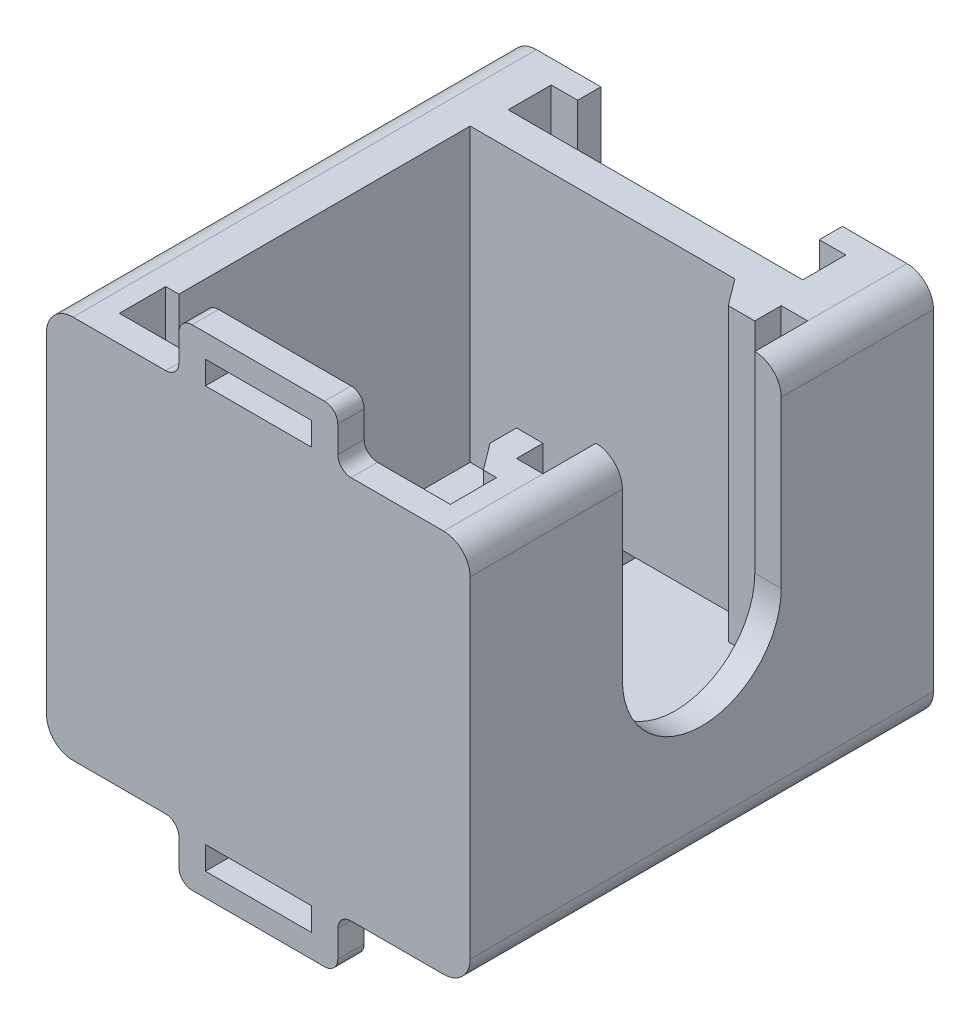
SolidWorks part; units mm, degrees
material "UNOBTANIUM"
ref_plane "Top Plane" through (0, 0, 0) normal (0, 0, 1) x (1, 0, 0)
ref_plane "Right Plane" through (0, 0, 0) normal (0, 1, 0) x (1, 0, 0)
ref_plane "Front Plane" through (0, 0, 0) normal (1, 0, 0) x (0, 0, -1)
ref_axis "x-axis" through (-17.6, 0, 0) along (1, 0, 0)
ref_axis "y-axis" through (0, -14.85, 0) along (0, 1, 0)
ref_axis "z-axis" through (0, 0, 36.75) along (0, 0, -1)
sketch "Sketch1" plane through (0, 0, 0) normal (0, 0, 1) x (1, 0, 0)
  line L1 (-16, 14.5) -> (16, 14.5)
  line L2 (-16, 14.5) -> (-16, -14.5)
  line L3 (-16, -14.5) -> (16, -14.5)
  line L4 (16, 14.5) -> (16, -14.5)
  line L5 (-16, 14.5) -> (16, -14.5) construction
  line L6 (-16, -14.5) -> (16, 14.5) construction
  point P0 (0, 0)
  dimension "D1" = 32
  dimension "D2" = 29
extrude "Boss-Extrude1" add sketch "Sketch1" along normal blind 35
fillet "Fillet1" radius 2 4 edges at (16, -14.5, 17.5) (16, 14.5, 17.5) (-16, -14.5, 17.5) (-16, 14.5, 17.5)
sketch "Sketch2" plane through (0, -14.5, 0) normal (0, -1, 0) x (1, 0, 0)
  line L0 (-9.125, 0) -> (-9.125, 1.75)
  line L1 (-14, 0) -> (14, 0) construction
  line L2 (-9.125, 1.75) -> (-11.125, 1.75)
  line L3 (-11.125, 1.75) -> (-11.125, 5)
  line L4 (-11.125, 5) -> (11.125, 5)
  line L5 (11.125, 5) -> (11.125, 1.75)
  line L6 (11.125, 1.75) -> (9.125, 1.75)
  line L7 (9.125, 1.75) -> (9.125, 0)
  line L9 (-9.125, 0) -> (9.125, 0)
  point P4 (0, 0)
  dimension "D1" = 18.25
  dimension "D2" = 1.75
  dimension "D3" = 3.25
  dimension "D4" = 22.25
extrude "Slot for Coil" cut sketch "Sketch2" against normal through all both and the other way through all
sketch "Sketch3" plane through (0, -14.5, 0) normal (0, -1, 0) x (1, 0, 0)
  line L0 (-9.125, 0) -> (-9.125, 1.75)
  line L1 (-9.125, 1.75) -> (-11.125, 1.75)
  line L2 (-11.125, 1.75) -> (-11.125, 5)
  line L3 (-11.125, 5) -> (11.125, 5)
  line L4 (11.125, 5) -> (11.125, 1.75)
  line L5 (11.125, 1.75) -> (9.125, 1.75)
  line L6 (9.125, 1.75) -> (9.125, 0)
  line L7 (9.125, 0) -> (-9.125, 0)
extrude "Boss-Extrude2" add sketch "Sketch3" against normal blind 7
sketch "Sketch4" plane through (0, 0, 1.75) normal (0, 0, -1) x (-1, 0, 0)
  line L1 (-9.125, 7.5) -> (-9.125, 6.5)
  line L2 (-9.125, 14.5) -> (-9.125, -7.5) construction
  arc A0 (-9.125, 7.5) -> (-9.125, 6.5) centre (-9.5, 7) cw
  dimension "D1" = 0.625
  dimension "D2" = 0.25
  dimension "D3" = 7
extrude "Boss-Extrude3" add sketch "Sketch4" along normal up to surface (1.75 mm away) up to face at (0, 1.1667, 0)
mirror "Mirror1" about plane through (0, 0, 0) normal (1, 0, 0) of "Boss-Extrude3"
sketch "Sketch5" plane through (0, 0, 0) normal (0, 0, -1) x (-1, 0, 0)
  line L0 (9.125, -7.5) -> (-9.125, -7.5) construction
  line L1 (-1, -7.5) -> (1, -7.5)
  line L2 (-1, -7.5) -> (-1, -14.5)
  line L3 (-1, -14.5) -> (1, -14.5)
  line L4 (1, -7.5) -> (1, -14.5)
  line L5 (14, -14.5) -> (-14, -14.5) construction
  point P8 (0, -7.5)
  dimension "D1" = 2
extrude "slot to feed in wire" cut sketch "Sketch5" against normal offset from surface (33 mm away) 2 up to face at (0, 0, 35)
sketch "Sketch6" plane through (0, 14.5, 0) normal (0, 1, 0) x (1, 0, 0)
  line L7 (11.5, -7.5) -> (-11.5, -7.5)
  line L8 (11.125, -5) -> (-11.125, -5) construction
  line L9 (0, -7.5) -> (0, -5) construction
  line L12 (-12.5, -33) -> (-12.5, -29.5)
  line L13 (-12.5, -29.5) -> (-11.5, -29.5)
  line L14 (-11.5, -29.5) -> (-11.5, -7.5)
  line L16 (12.5, -33) -> (12.5, -29.5)
  line L17 (12.5, -29.5) -> (11.5, -29.5)
  line L18 (11.5, -29.5) -> (11.5, -7.5)
  line L19 (-12.5, -33) -> (12.5, -33)
  line L20 (14, -35) -> (-14, -35) construction
  dimension "D1" = 2.5
  dimension "D2" = 3.5
  dimension "D3" = 1
  dimension "D4" = 23
  dimension "D5" = 2
  dimension "D6" = 3.5
  dimension "D7" = 1
extrude "slot fo PCB" cut sketch "Sketch6" against normal up to surface (22 mm away) up to face at (7.0833, -7.5, 2.25)
sketch "Sketch7" plane through (0, -14.5, 0) normal (0, -1, 0) x (1, 0, 0)
  line L0 (1, 0) -> (14, 0) construction
  line L1 (1, 0) -> (-1, 0)
  line L2 (1, 0) -> (1, 33)
  line L3 (1, 33) -> (-1, 33)
  line L4 (-1, 0) -> (-1, 33)
  line L5 (1, 33) -> (1, 0) construction
extrude "Boss-Extrude4" add sketch "Sketch7" against normal blind 0.25
fillet "Fillet2" radius 6 1 edges at (0, -14.25, 33)
ref_axis "Axis1" through (63.07, 0, 17.75) along (-1, 0, 0)
ref_plane "Plane1" through (0, 0, 17.75) normal (0, 0, -1) x (-1, 0, 0)
sketch "Sketch11" plane through (16, 0, 44) normal (1, 0, 0) x (0, 0, -1)
  line L0 (26.5, 25) -> (26.5, 0) construction
  line L4 (32.5, 25) -> (32.5, 0)
  line L5 (20.5, 25) -> (20.5, 0)
  line L6 (9, 12.5) -> (44, 12.5) construction
  line L7 (26.5, 0) -> (44, 0) construction
  line L8 (9, 12.5) -> (9, -12.5) construction
  arc A2 (32.5, 25) -> (20.5, 25) centre (26.5, 25) ccw
  arc A3 (20.5, 0) -> (32.5, 0) centre (26.5, 0) ccw
  point P2 (26.5, 12.5)
  dimension "D1" = 12
  dimension "D2" = 17.5
extrude "Rod Mount Slot" cut sketch "Sketch11" against normal up to next
sketch "Sketch14" plane through (0, 14.5, 0) normal (0, 1, 0) x (1, 0, 0)
  line L7 (14, -35) -> (14, -23.5) construction
  line L8 (11.5, -7.5) -> (14, -7.5)
  line L9 (11.5, -7.5) -> (11.5, -27.5)
  line L10 (11.5, -27.5) -> (14, -27.5)
  line L11 (14, -7.5) -> (14, -27.5)
  line L13 (12.5, -29.5) -> (11.5, -29.5) construction
  dimension "D2" = 2
extrude "Side cavity for mount plate" cut sketch "Sketch14" against normal up to surface (22 mm away) up to face at (-8.3333, -7.5, 23.3333)
sketch "Sketch16" plane through (0, 14.5, 0) normal (0, 1, 0) x (1, 0, 0)
  line L0 (1, -7.5) -> (14, -7.5) construction
  line L12 (12, -7.5) -> (10, -7.5)
  line L15 (12, -7.5) -> (12, -9.5)
  line L16 (12, -9.5) -> (10, -9.5)
  line L17 (10, -7.5) -> (10, -9.5)
  line L18 (14, -11.5) -> (14, -7.5) construction
  line L19 (14, -27.5) -> (11.5, -27.5) construction
  line L20 (12, -27.5) -> (10, -27.5)
  line L21 (12, -27.5) -> (12, -25.5)
  line L22 (12, -25.5) -> (10, -25.5)
  line L23 (10, -27.5) -> (10, -25.5)
  line L24 (14, -27.5) -> (14, -23.5) construction
  line L25 (14, -7.5) -> (14, -27.5) construction
  dimension "D6" = 2
  dimension "D7" = 2
  dimension "D8" = 2
  dimension "D9" = 2
  dimension "D10" = 4
extrude "Side stops for mount plate" add sketch "Sketch16" against normal up to surface (22 mm away) up to face at (-8.3333, -7.5, 23.3333)
sketch "Sketch20" plane through (0, 14.5, 0) normal (0, 1, 0) x (1, 0, 0)
  line L7 (11.5, -29.5) -> (10, -27.5)
  line L8 (10, -27.5) -> (11.5, -27.5)
  line L9 (11.5, -27.5) -> (11.5, -29.5)
  line L10 (10, -9.5) -> (8.5, -7.5)
  line L11 (10, -7.5) -> (-11.5, -7.5) construction
  line L12 (8.5, -7.5) -> (10, -7.5)
  line L13 (10, -7.5) -> (10, -9.5)
extrude "Boss-Extrude6" add sketch "Sketch20" against normal up to surface (22 mm away) up to face at (-8.3333, -7.5, 23.3333)
sketch "Sketch21" plane through (0, 14.5, 0) normal (0, 1, 0) x (-1, 0, 0)
  line L0 (0, 0) -> (0, 35) construction
  line L1 (-14, 35) -> (14, 35) construction
  line L2 (12.5, 33) -> (-12.5, 33) construction
  line L3 (-6, 35) -> (6, 35)
  line L4 (-6, 35) -> (-6, 33)
  line L5 (-6, 33) -> (6, 33)
  line L6 (6, 35) -> (6, 33)
  point P12 (0, 35)
  dimension "D1" = 12
extrude "Boss-Extrude7" add sketch "Sketch21" along normal blind 4
sketch "Sketch23" plane through (0, 0, 35) normal (0, 0, 1) x (1, 0, 0)
  line L0 (0, 0) -> (0, 18.5) construction
  line L1 (-6, 14.5) -> (-14, 14.5) construction
  line L3 (-4, 16.75) -> (4, 16.75)
  line L4 (-4, 16.75) -> (-4, 15)
  line L5 (-4, 15) -> (4, 15)
  line L6 (4, 16.75) -> (4, 15)
  line L7 (-6, 18.5) -> (6, 18.5) construction
  point P3 (0, 16.75)
  dimension "D1" = 1.75
  dimension "D2" = 8
  dimension "D3" = 0.5
extrude "Cut-Extrude7" cut sketch "Sketch23" against normal up to next
mirror "Mirror3" about plane through (0, 0, 0) normal (0, 1, 0) of "Boss-Extrude7", "Cut-Extrude7"
fillet "Fillet3" radius 1 8 edges at (-6, 14.5, 34) (6, 14.5, 34) (6, 18.5, 34) (-6, 18.5, 34) (6, -14.5, 34) (-6, -14.5, 34) (6, -18.5, 34) (-6, -18.5, 34)
sketch "Sketch26" plane through (-16, 0, 0) normal (1, 0, 0) x (0, 0, -1)
  circle A0 centre (-23.015, -2.89) radius 5.25
  point P2 (-25.005, -2.89)
  point P3 (-23.015, -2.89)
  dimension "D1" = 10.5
extrude "Cut-Extrude8" cut sketch "Sketch26" along normal up to next
